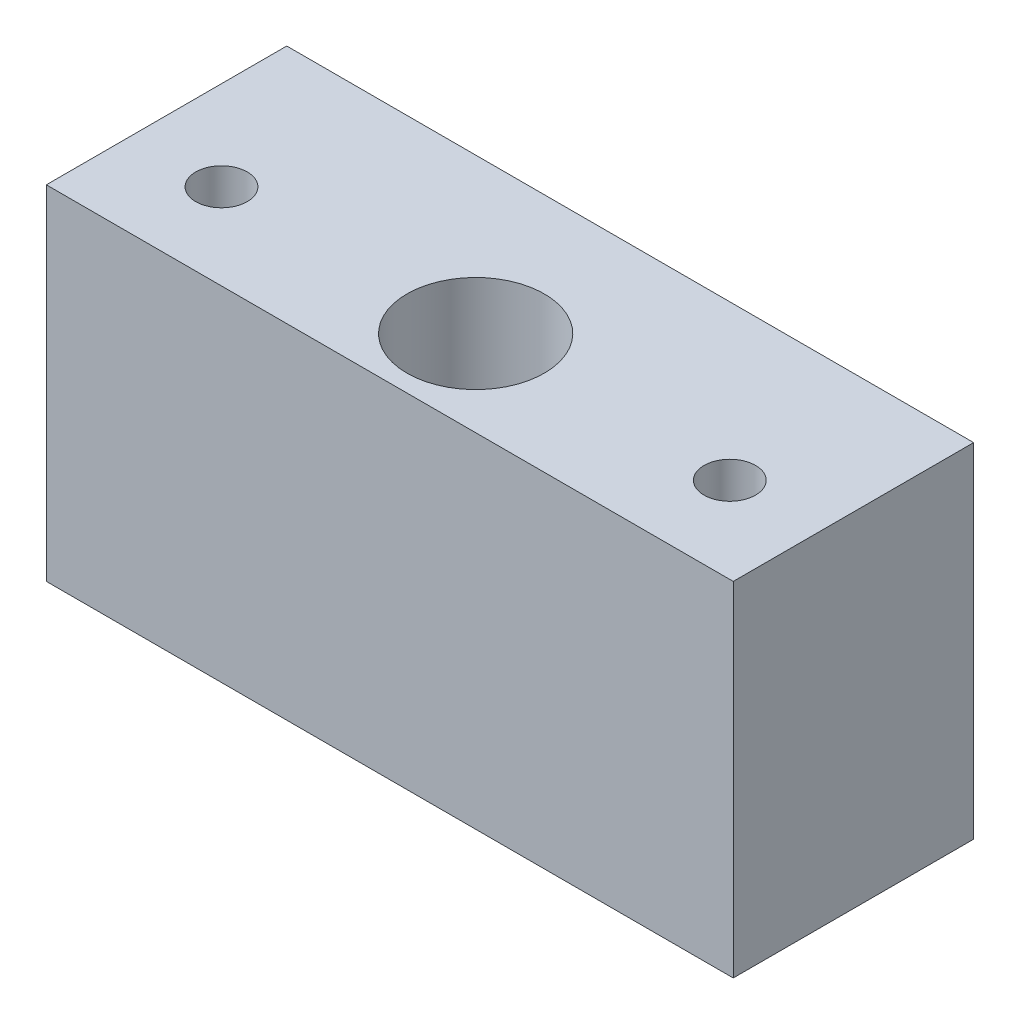
SolidWorks part; units mm, degrees
ref_plane "Front Plane" through (0, 0, 0) normal (0, 0, 1) x (1, 0, 0)
ref_plane "Top Plane" through (0, 0, 0) normal (0, 1, 0) x (1, 0, 0)
ref_plane "Right Plane" through (0, 0, 0) normal (1, 0, 0) x (0, 0, -1)
sketch "Sketch3" plane through (0, 0, 0) normal (0, 0, 1) x (1, 0, 0)
  line L1 (-50, -25) -> (50, -25)
  line L2 (-50, -25) -> (-50, 25)
  line L3 (-50, 25) -> (50, 25)
  line L4 (50, -25) -> (50, 25)
  line L5 (-50, -25) -> (50, 25) construction
  line L6 (-50, 25) -> (50, -25) construction
  point P0 (0, 0)
extrude "Boss-Extrude1" add sketch "Sketch3" along normal blind 25
sketch "Sketch5" plane through (0, 25, 0) normal (0, 1, 0) x (1, 0, 0)
  circle A0 centre (0, -12.5) radius 10
  circle A1 centre (37, -12.5) radius 3.75
  circle A2 centre (-37, -12.5) radius 3.75
  point P12 (0, -5)
extrude "Cut-Extrude1" cut sketch "Sketch5" against normal through all
sketch "Sketch7" plane through (0, 0, 0) normal (0, 0, -1) x (-1, 0, 0)
  circle A0 centre (32.5, 9.25) radius 2.5
  circle A1 centre (32.5, -9.25) radius 2.5
  circle A2 centre (-32.5, -9.25) radius 2.5
  circle A3 centre (-32.5, 9.25) radius 2.5
  point P8 (0, 0)
  point P11 (32.5, 0)
  point P14 (0, 0)
  point P16 (0, 0)
  point P23 (0, 0)
  dimension "D1" = 5
  dimension "D2" = 18.5
extrude "Cut-Extrude4" cut sketch "Sketch7" against normal blind 10
sketch "Sketch8" plane through (0, 0, 0) normal (0, 0, -1) x (-1, 0, 0)
  line L0 (-50, 25) -> (50, 25)
  line L1 (50, 25) -> (50, -25)
  line L2 (50, -25) -> (-50, -25)
  line L3 (-50, -25) -> (-50, 25)
  circle A0 centre (-32.5, 9.25) radius 2.5
  circle A1 centre (-32.5, -9.25) radius 2.5
  circle A2 centre (32.5, -9.25) radius 2.5
  circle A3 centre (32.5, 9.25) radius 2.5
extrude "Boss-Extrude2" add sketch "Sketch8" along normal blind 10
